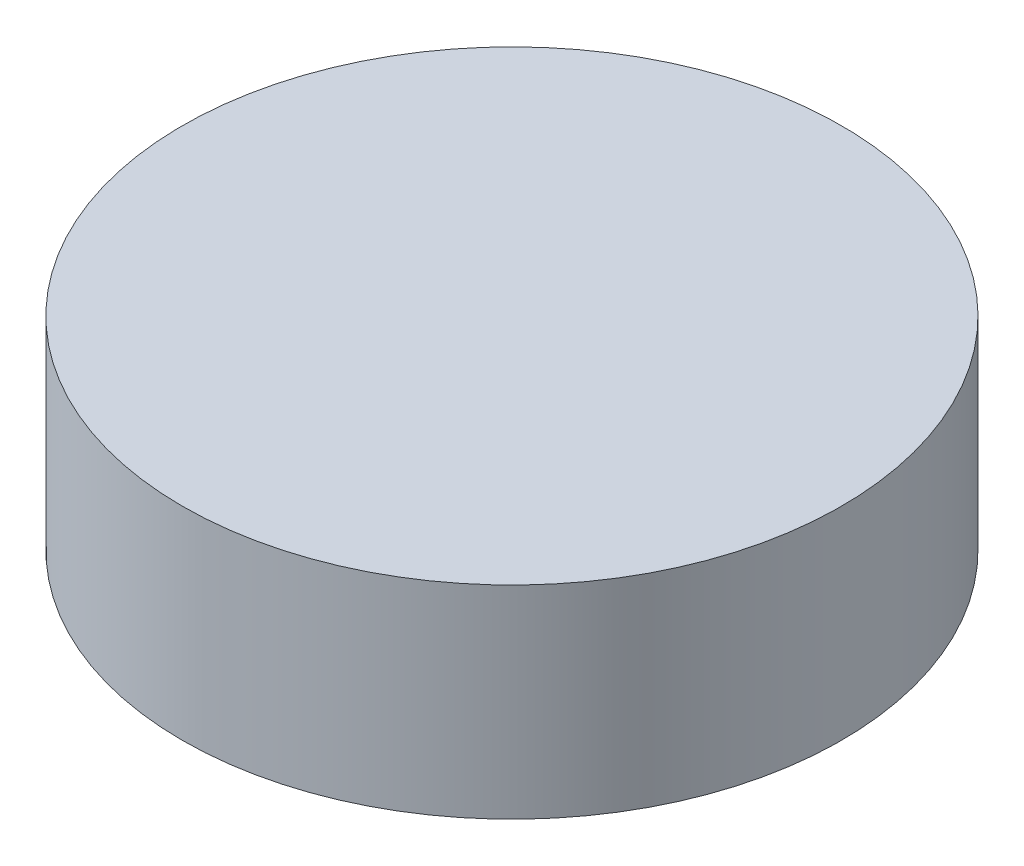
SolidWorks part; units mm, degrees
ref_plane "Front Plane" through (0, 0, 0) normal (0, 0, 1) x (1, 0, 0)
ref_plane "Top Plane" through (0, 0, 0) normal (0, 1, 0) x (1, 0, 0)
ref_plane "Right Plane" through (0, 0, 0) normal (1, 0, 0) x (0, 0, -1)
sketch "Sketch1" plane through (0, 0, 0) normal (0, 1, 0) x (1, 0, 0)
  circle A0 centre (0, 0) radius 32.5
  dimension "D1" = 65
extrude "Boss-Extrude1" add sketch "Sketch1" along normal mid plane 20
sketch "Sketch2" plane through (0, -10, 0) normal (0, -1, 0) x (1, 0, 0)
  circle A0 centre (0, 0) radius 25.5
  circle A1 centre (0, 0) radius 32.5 construction
  dimension "D1" = 7
extrude "Cut-Extrude1" cut sketch "Sketch2" against normal blind 15
